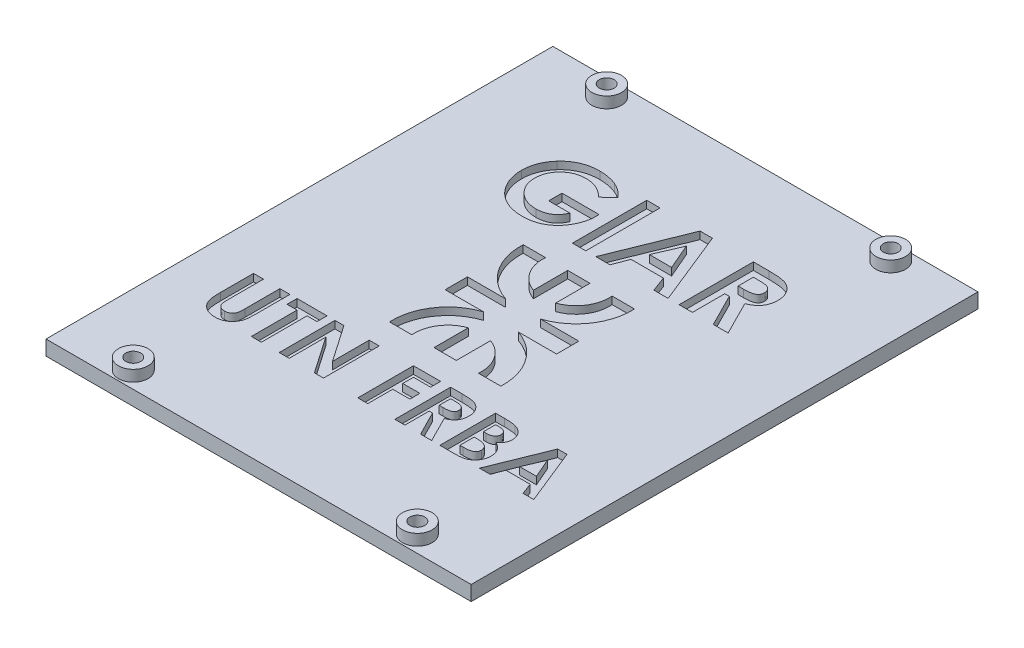
SolidWorks part; units mm, degrees
material "PLA_Tapa"
ref_plane "Front Plane" through (0, 0, 0) normal (0, 0, 1) x (1, 0, 0)
ref_plane "Top Plane" through (0, 0, 0) normal (0, 1, 0) x (1, 0, 0)
ref_plane "Right Plane" through (0, 0, 0) normal (1, 0, 0) x (0, 0, -1)
sketch "Sketch2" plane through (0, 0, 0) normal (0, 1, 0) x (1, 0, 0)
  line L0 (0, 0) -> (0, -50000) construction
  line L1 (-57.25, 68.25) -> (57.25, 68.25)
  line L2 (-57.25, 68.25) -> (-57.25, -68.25)
  line L3 (-57.25, -68.25) -> (57.25, -68.25)
  line L4 (57.25, 68.25) -> (57.25, -68.25)
  line L5 (-57.25, 68.25) -> (57.25, -68.25) construction
  line L6 (-57.25, -68.25) -> (57.25, 68.25) construction
  line L7 (0, 0) -> (50000, 0) construction
  circle A0 centre (-38.25, 63.75) radius 2
  circle A1 centre (-38.25, -63.75) radius 2
  circle A2 centre (38.25, -63.75) radius 2
  circle A3 centre (38.25, 63.75) radius 2
  point P0 (0, 0)
  dimension "D3" = 4
  dimension "D4" = 38.25
  dimension "D5" = 63.75
  dimension "D1" = 114.5
  dimension "D2" = 136.5
extrude "Boss-Extrude1" add sketch "Sketch2" along normal blind 4
sketch "Sketch3" plane through (0, 4, 0) normal (0, 1, 0) x (1, 0, 0)
  line L0 (-57.25, 25) -> (57.25, 25) construction
  line L1 (-9, 18) -> (-9, -18) construction
  line L2 (-15, 18) -> (15, 18) construction
  line L3 (-57.25, -45) -> (57.25, -45) construction
  line L4 (-47.25, 25) -> (57.25, 25) construction
  line L5 (-57.25, 68.25) -> (-57.25, -68.25) construction
  line L6 (57.25, -68.25) -> (57.25, 68.25) construction
  line L7 (-47.25, -45) -> (57.25, -45) construction
  line L8 (-57.25, -45) -> (-57.25, -68.25) construction
  line L9 (-57.25, -45) -> (-57.25, -25) construction
  line L10 (-57.25, -25) -> (-57.25, 25) construction
  line L11 (-57.25, 25) -> (-57.25, 45) construction
  line L12 (-57.25, 45) -> (-57.25, 68.25) construction
  line L13 (294.0315, 252.5659) -> (1544.0315, 252.5659) construction
  line L14 (-15, 18) -> (-15, -18) construction
  line L15 (-15, -18) -> (15, -18) construction
  line L16 (15, 18) -> (15, -18) construction
  line L17 (-15, 18) -> (15, -18) construction
  line L18 (-15, -18) -> (15, 18) construction
  line L19 (-3, 18) -> (-3, 8.7647) construction
  line L20 (3, 18) -> (3, 8.7647) construction
  line L21 (9, 18) -> (9, -18) construction
  line L22 (-15, 12) -> (15, 12) construction
  line L23 (-15, 6) -> (15, 6) construction
  line L24 (-15, 0) -> (15, 0) construction
  line L25 (-15, -6) -> (15, -6) construction
  line L26 (-15, -12) -> (15, -12) construction
  line L27 (-15, -3) -> (-4.6837, -3)
  line L28 (-15, 3) -> (-4.6837, 3)
  line L29 (-3, 18) -> (3, 18)
  line L30 (3, 18) -> (3, 8.7647)
  line L31 (3, -18) -> (-3, -18)
  line L32 (-3, -18) -> (-3, -8.7647)
  line L33 (-15, 3) -> (-15, -3)
  line L34 (15, 3) -> (15, -3)
  line L35 (0, -18) -> (0, -17.25) construction
  line L36 (-3, -8.7647) -> (-3, -18) construction
  line L37 (-3, 18) -> (-3, -18) construction
  line L38 (-4.6837, 3) -> (4.6837, 3) construction
  line L39 (3, -8.7647) -> (3, -18) construction
  line L40 (3, 18) -> (3, -18) construction
  line L41 (3, -8.7647) -> (3, -18)
  line L42 (4.6837, -3) -> (15, -3)
  line L43 (-15, -3) -> (15, -3) construction
  line L44 (-14.9812, -18) -> (-8.9687, -18)
  line L45 (8.9687, -18) -> (14.9812, -18)
  line L46 (0, 18) -> (0, 17.25)
  line L47 (-8.9687, 18) -> (-14.9812, 18)
  line L48 (-3, 8.7647) -> (-3, 18)
  line L49 (8.9687, 18) -> (14.9812, 18)
  line L52 (-15, 3) -> (15, 3) construction
  line L53 (4.6837, 3) -> (15, 3)
  arc A8 (14.9812, -18) -> (4.6837, -3) centre (0, -17.25) ccw
  arc A9 (8.9687, -18) -> (3, -8.7647) centre (0, -17.25) ccw
  arc A10 (-3, -8.7647) -> (-8.9687, -18) centre (0, -17.25) ccw
  arc A11 (-4.6837, -3) -> (-14.9812, -18) centre (0, -17.25) ccw
  arc A12 (-14.9812, 18) -> (-4.6837, 3) centre (0, 17.25) ccw
  arc A13 (-8.9687, 18) -> (-3, 8.7647) centre (0, 17.25) ccw
  arc A14 (3, 8.7647) -> (8.9687, 18) centre (0, 17.25) ccw
  arc A15 (4.6837, 3) -> (14.9812, 18) centre (0, 17.25) ccw
  text T0 "GIAR" font "Century Gothic" height 20
  text T1 "UTN FRBA" font "Century Gothic" height 20
  dimension "D3" = 50
  dimension "D6" = 6
  dimension "D15" = 3
  dimension "D17" = 0.75
  dimension "D18" = 0.75
  dimension "D1" = 20
  dimension "D2" = 20
  dimension "D4" = 36
  dimension "D5" = 30
  dimension "D7" = 6
  dimension "D8" = 6
  dimension "D9" = 6
  dimension "D10" = 6
  dimension "D11" = 6
  dimension "D12" = 6
  dimension "D13" = 6
  dimension "D14" = 6
  dimension "D16" = 3
extrude "Cut-Extrude1" cut sketch "Sketch3" against normal blind 2 contours L53 A15 L49 A14 L30 L29 L48 A13 L47 A12 L28 L33 L27 A11 L44 A10 L32 L31 L41 A9 L45 A8 L42 L34 region at (0, 4, 0)
sketch "Sketch4" plane through (0, 4, 4) normal (0, 1, 0) x (1, 0, 0)
  line L0 (-57.25, 29) -> (57.25, 29) construction
  line L3 (-57.25, -36) -> (57.25, -36) construction
  line L4 (-47.25, 29) -> (57.25, 29) construction
  line L5 (-8.9687, 22) -> (-14.9812, 22) construction
  line L6 (-14.9812, -14) -> (-8.9687, -14) construction
  line L7 (-47.25, -36) -> (57.25, -36) construction
  line L8 (-57.25, 72.25) -> (-57.25, -64.25) construction
  line L9 (-57.25, -36) -> (-57.25, -21) construction
  line L10 (-57.25, -21) -> (-57.25, 29) construction
  line L11 (-57.25, 29) -> (-57.25, 49) construction
  line L13 (294.0315, 252.5659) -> (1544.0315, 252.5659) construction
  line L17 (57.25, -64.25) -> (57.25, 72.25) construction
  text T0 "GIAR" font "Century Gothic" height 20
  text T1 "UTN FRBA" font "Century Gothic" height 15
  dimension "D3" = 7
  dimension "D1" = 15
  dimension "D2" = 20
  dimension "D4" = 7
extrude "Cut-Extrude2" cut sketch "Sketch4" against normal blind 2
sketch "Sketch5" plane through (0, 4, 0) normal (0, 1, 0) x (1, 0, 0)
  circle A0 centre (38.25, -63.75) radius 2 construction
  circle A1 centre (-38.25, -63.75) radius 2 construction
  circle A2 centre (38.25, 63.75) radius 2 construction
  circle A3 centre (-38.25, 63.75) radius 2 construction
  circle A12 centre (38.25, -63.75) radius 2
  circle A13 centre (-38.25, -63.75) radius 2
  circle A14 centre (38.25, 63.75) radius 2
  circle A15 centre (-38.25, 63.75) radius 2
  circle A16 centre (38.25, -63.75) radius 4
  circle A17 centre (-38.25, -63.75) radius 4
  circle A18 centre (38.25, 63.75) radius 4
  circle A19 centre (-38.25, 63.75) radius 4
  dimension "D1" = 2
extrude "Boss-Extrude2" add sketch "Sketch5" along normal blind 3
